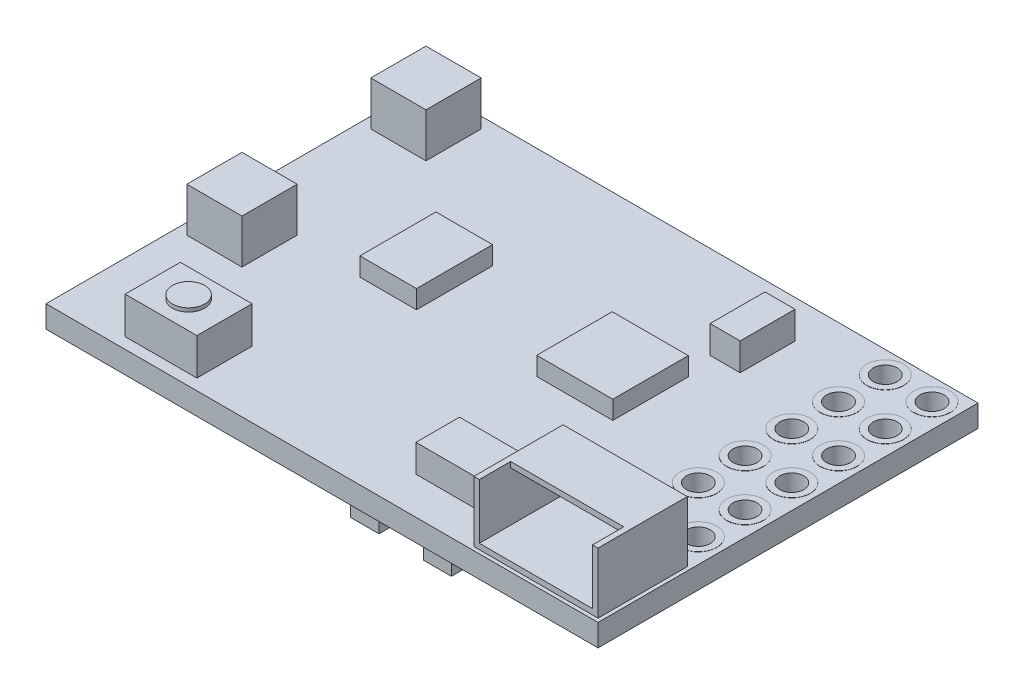
SolidWorks part; units mm, degrees
ref_plane "Front Plane" through (0, 0, 0) normal (0, 0, 1) x (1, 0, 0)
ref_plane "Top Plane" through (0, 0, 0) normal (0, 1, 0) x (1, 0, 0)
ref_plane "Right Plane" through (0, 0, 0) normal (1, 0, 0) x (0, 0, -1)
sketch "Sketch1" plane through (0, 0, 0) normal (0, 1, 0) x (1, 0, 0)
  line L1 (-15, 10.325) -> (15, 10.325)
  line L2 (-15, 10.325) -> (-15, -10.325)
  line L3 (-15, -10.325) -> (15, -10.325)
  line L4 (15, 10.325) -> (15, -10.325)
  line L5 (-15, 10.325) -> (15, -10.325) construction
  line L6 (-15, -10.325) -> (15, 10.325) construction
  point P0 (0, 0)
  dimension "D1" = 30
  dimension "D2" = 20.65
extrude "Boss-Extrude1" add sketch "Sketch1" along normal blind 1.2
sketch "Sketch2" plane through (0, 1.2, 0) normal (0, 1, 0) x (1, 0, 0)
  line L0 (13.7, 10.325) -> (13.7, -10.325) construction
  line L1 (15, 10.325) -> (-15, 10.325) construction
  line L2 (-15, -10.325) -> (15, -10.325) construction
  line L3 (11.16, 9.125) -> (13.7, 9.125) construction
  line L4 (15, -10.325) -> (15, 10.325) construction
  line L5 (13.7, 9.125) -> (13.7, 6.585) construction
  circle A0 centre (13.7, 9.125) radius 0.65
  circle A1 centre (11.16, 9.125) radius 0.65
  circle A2 centre (11.16, 6.585) radius 0.65
  circle A3 centre (11.16, 4.045) radius 0.65
  circle A4 centre (11.16, 1.505) radius 0.65
  circle A5 centre (11.16, -1.035) radius 0.65
  circle A6 centre (11.16, -3.575) radius 0.65
  circle A7 centre (13.7, 6.585) radius 0.65
  circle A8 centre (13.7, 4.045) radius 0.65
  circle A9 centre (13.7, 1.505) radius 0.65
  circle A10 centre (13.7, -1.035) radius 0.65
  circle A11 centre (13.7, -3.575) radius 0.65
  dimension "D3" = 1.3
  dimension "D1" = 1.3
  dimension "D2" = 2
  dimension "D4" = 1.2
  dimension "D6" = 2.54
  dimension "D5" = 6
extrude "Cut-Extrude1" cut sketch "Sketch2" against normal up to next
sketch "Sketch3" plane through (0, 1.2, 0) normal (0, 1, 0) x (1, 0, 0)
  line L0 (-15, -10.325) -> (15, -10.325) construction
  line L1 (14.8, -10.125) -> (8.05, -10.125)
  line L2 (14.8, -10.125) -> (14.8, -5.275)
  line L3 (14.8, -5.275) -> (8.05, -5.275)
  line L4 (8.05, -10.125) -> (8.05, -5.275)
  line L5 (15, -10.325) -> (15, 10.325) construction
  point P5 (14.6082, -9.9313)
  dimension "D1" = 6.75
  dimension "D2" = 4.85
  dimension "D3" = 0.2
  dimension "D4" = 0.2
extrude "Boss-Extrude2" add sketch "Sketch3" along normal blind 3.3
sketch "Sketch4" plane through (0, 1.2, 0) normal (0, 1, 0) x (1, 0, 0)
  line L0 (15, 10.325) -> (-15, 10.325) construction
  line L1 (-14.4, 9.725) -> (-11.4, 9.725)
  line L2 (-14.4, 9.725) -> (-14.4, 6.725)
  line L3 (-14.4, 6.725) -> (-11.4, 6.725)
  line L4 (-11.4, 9.725) -> (-11.4, 6.725)
  line L5 (-15, 10.325) -> (-15, -10.325) construction
  line L6 (-15, 3.225) -> (15, 3.225) construction
  line L7 (15, -10.325) -> (15, 10.325) construction
  line L8 (-14.4, -0.275) -> (-11.4, -0.275)
  line L9 (-11.4, -3.275) -> (-11.4, -0.275)
  line L10 (-14.4, -3.275) -> (-11.4, -3.275)
  line L11 (-14.4, -3.275) -> (-14.4, -0.275)
  dimension "D1" = 3
  dimension "D2" = 3
  dimension "D3" = 0.6
  dimension "D4" = 0.6
  dimension "D5" = 7
extrude "Boss-Extrude3" add sketch "Sketch4" along normal blind 2.4
sketch "Sketch5" plane through (0, 1.2, 0) normal (0, 1, 0) x (1, 0, 0)
  line L0 (-15, 10.325) -> (-15, -10.325) construction
  line L1 (-11.3, -9.725) -> (-7.4, -9.725)
  line L2 (-11.3, -9.725) -> (-11.3, -6.725)
  line L3 (-11.3, -6.725) -> (-7.4, -6.725)
  line L4 (-7.4, -9.725) -> (-7.4, -6.725)
  line L5 (-15, -10.325) -> (15, -10.325) construction
  dimension "D1" = 3.9
  dimension "D2" = 3
  dimension "D3" = 3.7
  dimension "D4" = 0.6
extrude "Boss-Extrude4" add sketch "Sketch5" along normal blind 2
sketch "Sketch6" plane through (0, 3.2, 0) normal (0, 1, 0) x (1, 0, 0)
  line L0 (-11.3, -8.225) -> (-7.4, -8.225) construction
  line L1 (-11.3, -6.725) -> (-11.3, -9.725) construction
  line L2 (-7.4, -9.725) -> (-7.4, -6.725) construction
  line L3 (-9.35, -6.725) -> (-9.35, -9.725) construction
  line L4 (-7.4, -6.725) -> (-11.3, -6.725) construction
  line L5 (-11.3, -9.725) -> (-7.4, -9.725) construction
  circle A0 centre (-9.35, -8.225) radius 0.875
  dimension "D1" = 1.75
extrude "Boss-Extrude5" add sketch "Sketch6" along normal blind 0.2
sketch "Sketch7" plane through (0, 4.5, 0) normal (0, 1, 0) x (1, 0, 0)
  line L0 (11.425, -5.275) -> (11.425, -10.125) construction
  line L1 (14.8, -5.275) -> (8.05, -5.275) construction
  line L2 (8.05, -10.125) -> (14.8, -10.125) construction
  line L3 (8.05, -10.125) -> (14.8, -10.125) construction
  line L4 (8.35, -10.125) -> (14.5, -10.125)
  line L5 (8.35, -10.125) -> (8.35, -8.425)
  line L6 (8.35, -8.425) -> (14.5, -8.425)
  line L7 (14.5, -10.125) -> (14.5, -8.425)
  line L8 (8.05, -5.275) -> (8.05, -10.125) construction
  point P12 (11.425, -8.425)
  dimension "D1" = 0.3
  dimension "D2" = 1.7
extrude "Cut-Extrude2" cut sketch "Sketch7" against normal offset from surface (3 mm away) 0.3 up to face at (11.16, 1.2, 4.225)
sketch "Sketch8" plane through (0, 0, 8.425) normal (0, 0, 1) x (1, 0, 0)
  line L0 (14.5, 1.5) -> (14.5, 4.5) construction
  line L1 (8.35, 1.5) -> (14.5, 1.5)
  line L2 (8.35, 1.5) -> (8.35, 4.2)
  line L3 (8.35, 4.2) -> (14.5, 4.2)
  line L4 (14.5, 1.5) -> (14.5, 4.2)
  line L5 (14.5, 4.5) -> (8.35, 4.5) construction
  dimension "D1" = 0.3
extrude "Cut-Extrude3" cut sketch "Sketch8" against normal offset from surface (2.85 mm away) 0.3 up to face at (11.425, 2.85, 5.275)
sketch "Sketch9" plane through (0, 1.2, 0) normal (0, 1, 0) x (1, 0, 0)
  line L1 (5.896, 3.685) -> (1.7624, 3.685)
  line L2 (5.896, 3.685) -> (5.896, -0.4166)
  line L3 (5.896, -0.4166) -> (1.7624, -0.4166)
  line L4 (1.7624, 3.685) -> (1.7624, -0.4166)
  line L5 (-7.7224, 3.5888) -> (-4.6463, 3.5888)
  line L6 (-7.7224, 3.5888) -> (-7.7224, -0.5447)
  line L7 (-7.7224, -0.5447) -> (-4.6463, -0.5447)
  line L8 (-4.6463, 3.5888) -> (-4.6463, -0.5447)
extrude "Boss-Extrude6" add sketch "Sketch9" along normal blind 1
sketch "Sketch10" plane through (0, 1.2, 0) normal (0, 1, 0) x (1, 0, 0)
  line L1 (7.1136, 8.2672) -> (5.4794, 8.2672)
  line L2 (7.1136, 8.2672) -> (7.1136, 5.2871)
  line L3 (7.1136, 5.2871) -> (5.4794, 5.2871)
  line L4 (5.4794, 8.2672) -> (5.4794, 5.2871)
  line L5 (7.5302, -5.928) -> (3.0762, -5.928)
  line L6 (7.5302, -5.928) -> (7.5302, -8.2992)
  line L7 (7.5302, -8.2992) -> (3.0762, -8.2992)
  line L8 (3.0762, -5.928) -> (3.0762, -8.2992)
  point P12 (0, 0)
  point P13 (5.4794, 5.2871)
  point P14 (7.1136, 8.2672)
  point P15 (7.5302, -5.928)
  point P16 (3.0762, -8.2992)
extrude "Boss-Extrude7" add sketch "Sketch10" along normal blind 1.5
sketch "Sketch11" plane through (0, 0, 0) normal (0, -1, 0) x (1, 0, 0)
  line L1 (-6.3538, 2.621) -> (0.4959, 2.621)
  line L2 (-6.3538, 2.621) -> (-6.3538, -4.2287)
  line L3 (-6.3538, -4.2287) -> (0.4959, -4.2287)
  line L4 (0.4959, 2.621) -> (0.4959, -4.2287)
  line L6 (-15, -10.325) -> (-15, 10.325) construction
  line L7 (6.1467, 9.4396) -> (4.628, 9.4396)
  line L8 (6.1467, 9.4396) -> (6.1467, 6.4332)
  line L9 (6.1467, 6.4332) -> (4.628, 6.4332)
  line L10 (4.628, 9.4396) -> (4.628, 6.4332)
  line L11 (2.1795, 9.4086) -> (0.6298, 9.4086)
  line L12 (2.1795, 9.4086) -> (2.1795, 6.3402)
  line L13 (2.1795, 6.3402) -> (0.6298, 6.3402)
  line L14 (0.6298, 9.4086) -> (0.6298, 6.3402)
  line L15 (4.9689, 5.6274) -> (6.1467, 5.6274)
  line L16 (4.9689, 5.6274) -> (4.9689, 2.8689)
  line L17 (4.9689, 2.8689) -> (6.1467, 2.8689)
  line L18 (6.1467, 5.6274) -> (6.1467, 2.8689)
  line L19 (-15, -4.3837) -> (-12.1398, -4.3837)
  line L20 (-15, -4.3837) -> (-15, -8.5679)
  line L21 (-15, -8.5679) -> (-12.1398, -8.5679)
  line L22 (-12.1398, -4.3837) -> (-12.1398, -8.5679)
  line L23 (-13.5965, 3.7987) -> (-11.21, 3.7987)
  line L24 (-13.5965, 3.7987) -> (-13.5965, 0.6993)
  line L25 (-13.5965, 0.6993) -> (-11.21, 0.6993)
  line L26 (-11.21, 3.7987) -> (-11.21, 0.6993)
  line L27 (-10.0012, -6.3053) -> (-8.7304, -6.3053)
  line L28 (-10.0012, -6.3053) -> (-10.0012, -9.4667)
  line L29 (-10.0012, -9.4667) -> (-8.7304, -9.4667)
  line L30 (-8.7304, -6.3053) -> (-8.7304, -9.4667)
  point P4 (-6.1579, -4.3258)
  point P5 (0.1958, 2.652)
  point P6 (0, -3.7328)
  point P7 (6.1467, 5.6274)
  point P32 (4.9689, 2.8689)
  point P33 (0.6298, 9.4086)
  point P34 (2.1795, 6.3402)
  point P35 (4.628, 9.4396)
  point P36 (6.1467, 6.4332)
  point P37 (-13.5965, 0.6993)
  point P38 (-11.21, 3.7987)
  point P39 (-15, -8.5679)
  point P42 (-12.1398, -4.3837)
  point P43 (-10.0012, -9.4667)
  point P44 (-8.7304, -6.3053)
extrude "Boss-Extrude8" add sketch "Sketch11" along normal blind 1.5
sketch "Sketch12" plane through (0, 1.2, 0) normal (0, 1, 0) x (1, 0, 0)
  circle A0 centre (11.16, 9.125) radius 1
  circle A1 centre (13.7, 9.125) radius 1
  circle A2 centre (13.7, 6.585) radius 1
  circle A3 centre (11.16, 6.585) radius 1
  circle A4 centre (11.16, 4.045) radius 1
  circle A5 centre (13.7, 4.045) radius 1
  circle A6 centre (13.7, 1.505) radius 1
  circle A7 centre (11.16, 1.505) radius 1
  circle A8 centre (11.16, -1.035) radius 1
  circle A9 centre (11.16, -3.575) radius 1
  circle A10 centre (13.7, -3.575) radius 1
  circle A11 centre (13.7, -1.035) radius 1
  circle A12 centre (11.16, -3.575) radius 0.65 construction
  circle A13 centre (13.7, -3.575) radius 0.65 construction
  circle A14 centre (13.7, -1.035) radius 0.65 construction
  circle A15 centre (11.16, -1.035) radius 0.65 construction
  circle A16 centre (11.16, 1.505) radius 0.65 construction
  circle A17 centre (13.7, 1.505) radius 0.65 construction
  circle A18 centre (13.7, 4.045) radius 0.65 construction
  circle A19 centre (11.16, 4.045) radius 0.65 construction
  circle A20 centre (11.16, 6.585) radius 0.65 construction
  circle A21 centre (13.7, 6.585) radius 0.65 construction
  circle A22 centre (13.7, 9.125) radius 0.65 construction
  circle A23 centre (11.16, 9.125) radius 0.65 construction
  circle A24 centre (11.16, -3.575) radius 0.65
  circle A25 centre (13.7, -3.575) radius 0.65
  circle A26 centre (13.7, -1.035) radius 0.65
  circle A27 centre (11.16, -1.035) radius 0.65
  circle A28 centre (11.16, 1.505) radius 0.65
  circle A29 centre (13.7, 1.505) radius 0.65
  circle A30 centre (13.7, 4.045) radius 0.65
  circle A31 centre (11.16, 4.045) radius 0.65
  circle A32 centre (11.16, 6.585) radius 0.65
  circle A33 centre (13.7, 6.585) radius 0.65
  circle A34 centre (13.7, 9.125) radius 0.65
  circle A35 centre (11.16, 9.125) radius 0.65
  dimension "D1" = 2
extrude "Boss-Extrude9" add sketch "Sketch12" along normal blind 0.01
ref_plane "Plane1" through (0, 0.6, 0) normal (0, 1, 0) x (1, 0, 0)
mirror "Mirror1" about plane through (0, 0.6, 0) normal (0, 1, 0) of "Boss-Extrude9"
